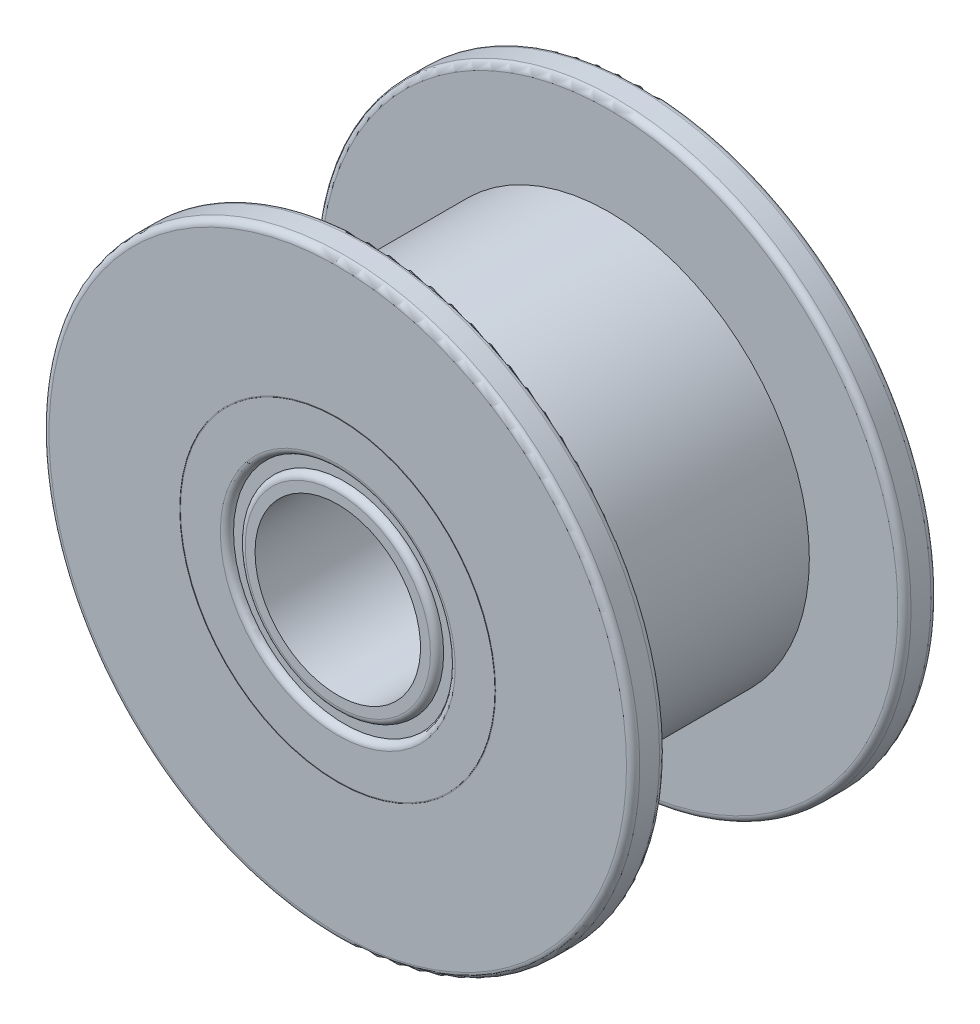
SolidWorks part; units mm, degrees
material "1060-H12 Válcovaný drát (SS)"
ref_plane "Front Plane" through (0, 0, 0) normal (0, 0, 1) x (1, 0, 0)
ref_plane "Top Plane" through (0, 0, 0) normal (0, 1, 0) x (1, 0, 0)
ref_plane "Right Plane" through (0, 0, 0) normal (1, 0, 0) x (0, 0, -1)
sketch "Skica1" plane through (0, 0, 0) normal (0, 0, 1) x (1, 0, 0)
  line L0 (0, 0) -> (0, 6.1) construction
  line L1 (0, 6.1) -> (-0.5, 6.0795) construction
  line L2 (0, 6.1) -> (0.5, 6.0795) construction
  line L3 (-0.5, 6.0795) -> (-0.5, 5.5776)
  line L4 (-0.5, 5.5776) -> (-1.2481, 5.4592) construction
  line L5 (0.5, 6.0795) -> (0.5, 5.5776)
  line L6 (1.4031, 5.9364) -> (1.2481, 5.4592)
  line L7 (2.3542, 5.6274) -> (2.1991, 5.1501)
  line L8 (3.1689, 5.2123) -> (2.8739, 4.8063)
  line L9 (3.9779, 4.6245) -> (3.683, 4.2185)
  line L10 (4.6245, 3.9779) -> (4.2185, 3.683)
  line L11 (5.2123, 3.1689) -> (4.8063, 2.8739)
  line L12 (5.6274, 2.3542) -> (5.1501, 2.1991)
  line L13 (5.9364, 1.4031) -> (5.4592, 1.2481)
  line L14 (6.0795, 0.5) -> (5.5776, 0.5)
  line L15 (6.0795, -0.5) -> (5.5776, -0.5)
  line L16 (5.9364, -1.4031) -> (5.4592, -1.2481)
  line L17 (5.6274, -2.3542) -> (5.1501, -2.1991)
  line L18 (5.2123, -3.1689) -> (4.8063, -2.8739)
  line L19 (4.6245, -3.9779) -> (4.2185, -3.683)
  line L20 (3.9779, -4.6245) -> (3.683, -4.2185)
  line L21 (3.1689, -5.2123) -> (2.8739, -4.8063)
  line L22 (2.3542, -5.6274) -> (2.1991, -5.1501)
  line L23 (1.4031, -5.9364) -> (1.2481, -5.4592)
  line L24 (0.5, -6.0795) -> (0.5, -5.5776)
  line L25 (-0.5, -6.0795) -> (-0.5, -5.5776)
  line L26 (-1.4031, -5.9364) -> (-1.2481, -5.4592)
  line L27 (-2.3542, -5.6274) -> (-2.1991, -5.1501)
  line L28 (-3.1689, -5.2123) -> (-2.8739, -4.8063)
  line L29 (-3.9779, -4.6245) -> (-3.683, -4.2185)
  line L30 (-4.6245, -3.9779) -> (-4.2185, -3.683)
  line L31 (-5.2123, -3.1689) -> (-4.8063, -2.8739)
  line L32 (-5.6274, -2.3542) -> (-5.1501, -2.1991)
  line L33 (-5.9364, -1.4031) -> (-5.4592, -1.2481)
  line L34 (-6.0795, -0.5) -> (-5.5776, -0.5)
  line L35 (-6.0795, 0.5) -> (-5.5776, 0.5)
  line L36 (-5.9364, 1.4031) -> (-5.4592, 1.2481)
  line L37 (-5.6274, 2.3542) -> (-5.1501, 2.1991)
  line L38 (-5.2123, 3.1689) -> (-4.8063, 2.8739)
  line L39 (-4.6245, 3.9779) -> (-4.2185, 3.683)
  line L40 (-3.9779, 4.6245) -> (-3.683, 4.2185)
  line L41 (-3.1689, 5.2123) -> (-2.8739, 4.8063)
  line L42 (-2.3542, 5.6274) -> (-2.1991, 5.1501)
  line L43 (-1.4031, 5.9364) -> (-1.2481, 5.4592)
  circle A0 centre (0, 0) radius 6.1 construction
  circle A1 centre (0, 0) radius 5.6 construction
  arc A2 (-1.2481, 5.4592) -> (-0.5, 5.5776) centre (0, 0) cw
  arc A3 (-0.5, 6.0795) -> (0.5, 6.0795) centre (0, 0) cw
  arc A4 (0.5, 5.5776) -> (1.2481, 5.4592) centre (0, 0) cw
  arc A5 (1.4031, 5.9364) -> (2.3542, 5.6274) centre (0, 0) cw
  arc A6 (2.1991, 5.1501) -> (2.8739, 4.8063) centre (0, 0) cw
  arc A7 (3.1689, 5.2123) -> (3.9779, 4.6245) centre (0, 0) cw
  arc A8 (3.683, 4.2185) -> (4.2185, 3.683) centre (0, 0) cw
  arc A9 (4.6245, 3.9779) -> (5.2123, 3.1689) centre (0, 0) cw
  arc A10 (4.8063, 2.8739) -> (5.1501, 2.1991) centre (0, 0) cw
  arc A11 (5.6274, 2.3542) -> (5.9364, 1.4031) centre (0, 0) cw
  arc A12 (5.4592, 1.2481) -> (5.5776, 0.5) centre (0, 0) cw
  arc A13 (6.0795, 0.5) -> (6.0795, -0.5) centre (0, 0) cw
  arc A14 (5.5776, -0.5) -> (5.4592, -1.2481) centre (0, 0) cw
  arc A15 (5.9364, -1.4031) -> (5.6274, -2.3542) centre (0, 0) cw
  arc A16 (5.1501, -2.1991) -> (4.8063, -2.8739) centre (0, 0) cw
  arc A17 (5.2123, -3.1689) -> (4.6245, -3.9779) centre (0, 0) cw
  arc A18 (4.2185, -3.683) -> (3.683, -4.2185) centre (0, 0) cw
  arc A19 (3.9779, -4.6245) -> (3.1689, -5.2123) centre (0, 0) cw
  arc A20 (2.8739, -4.8063) -> (2.1991, -5.1501) centre (0, 0) cw
  arc A21 (2.3542, -5.6274) -> (1.4031, -5.9364) centre (0, 0) cw
  arc A22 (1.2481, -5.4592) -> (0.5, -5.5776) centre (0, 0) cw
  arc A23 (0.5, -6.0795) -> (-0.5, -6.0795) centre (0, 0) cw
  arc A24 (-0.5, -5.5776) -> (-1.2481, -5.4592) centre (0, 0) cw
  arc A25 (-1.4031, -5.9364) -> (-2.3542, -5.6274) centre (0, 0) cw
  arc A26 (-2.1991, -5.1501) -> (-2.8739, -4.8063) centre (0, 0) cw
  arc A27 (-3.1689, -5.2123) -> (-3.9779, -4.6245) centre (0, 0) cw
  arc A28 (-3.683, -4.2185) -> (-4.2185, -3.683) centre (0, 0) cw
  arc A29 (-4.6245, -3.9779) -> (-5.2123, -3.1689) centre (0, 0) cw
  arc A30 (-4.8063, -2.8739) -> (-5.1501, -2.1991) centre (0, 0) cw
  arc A31 (-5.6274, -2.3542) -> (-5.9364, -1.4031) centre (0, 0) cw
  arc A32 (-5.4592, -1.2481) -> (-5.5776, -0.5) centre (0, 0) cw
  arc A33 (-6.0795, -0.5) -> (-6.0795, 0.5) centre (0, 0) cw
  arc A34 (-5.5776, 0.5) -> (-5.4592, 1.2481) centre (0, 0) cw
  arc A35 (-5.9364, 1.4031) -> (-5.6274, 2.3542) centre (0, 0) cw
  arc A36 (-5.1501, 2.1991) -> (-4.8063, 2.8739) centre (0, 0) cw
  arc A37 (-5.2123, 3.1689) -> (-4.6245, 3.9779) centre (0, 0) cw
  arc A38 (-4.2185, 3.683) -> (-3.683, 4.2185) centre (0, 0) cw
  arc A39 (-3.9779, 4.6245) -> (-3.1689, 5.2123) centre (0, 0) cw
  arc A40 (-2.8739, 4.8063) -> (-2.1991, 5.1501) centre (0, 0) cw
  arc A41 (-2.3542, 5.6274) -> (-1.4031, 5.9364) centre (0, 0) cw
  point P110 (0, 0)
  dimension "D1" = 12.2
  dimension "D2" = 0.5
  dimension "D3" = 1
  dimension "D5" = 20
extrude "Přidat vysunutím1" add sketch "Skica1" along normal blind 7.2
fillet "Zaoblit1" radius 0.2 80 edges at (-2.1991, 5.1501, 3.6) (-2.3542, 5.6274, 3.6) (-1.4031, 5.9364, 3.6) (-1.2481, 5.4592, 3.6) (-0.5, 5.5776, 3.6) (-0.5, 6.0795, 3.6) (0.5, 6.0795, 3.6) (0.5, 5.5776, 3.6) (1.2481, 5.4592, 3.6) (1.4031, 5.9364, 3.6) (2.3542, 5.6274, 3.6) (2.1991, 5.1501, 3.6) (-2.8739, 4.8063, 3.6) (-3.1689, 5.2123, 3.6) (-3.9779, 4.6245, 3.6) (-3.683, 4.2185, 3.6) (-4.2185, 3.683, 3.6) (-4.6245, 3.9779, 3.6) (-5.2123, 3.1689, 3.6) (-4.8063, 2.8739, 3.6) (-5.1501, 2.1991, 3.6) (-5.6274, 2.3542, 3.6) (-5.9364, 1.4031, 3.6) (-5.4592, 1.2481, 3.6) (-5.5776, 0.5, 3.6) (-6.0795, 0.5, 3.6) (-6.0795, -0.5, 3.6) (-5.5776, -0.5, 3.6) (-5.4592, -1.2481, 3.6) (-5.9364, -1.4031, 3.6) (-5.6274, -2.3542, 3.6) (-5.1501, -2.1991, 3.6) (-4.8063, -2.8739, 3.6) (-5.2123, -3.1689, 3.6) (-4.6245, -3.9779, 3.6) (-4.2185, -3.683, 3.6) (-3.683, -4.2185, 3.6) (-3.9779, -4.6245, 3.6) (-3.1689, -5.2123, 3.6) (-2.8739, -4.8063, 3.6) (-2.1991, -5.1501, 3.6) (-2.3542, -5.6274, 3.6) (-1.4031, -5.9364, 3.6) (-1.2481, -5.4592, 3.6) (-0.5, -5.5776, 3.6) (-0.5, -6.0795, 3.6) (0.5, -6.0795, 3.6) (0.5, -5.5776, 3.6) (1.2481, -5.4592, 3.6) (1.4031, -5.9364, 3.6) (2.3542, -5.6274, 3.6) (2.1991, -5.1501, 3.6) (2.8739, -4.8063, 3.6) (3.1689, -5.2123, 3.6) (3.9779, -4.6245, 3.6) (3.683, -4.2185, 3.6) (4.2185, -3.683, 3.6) (4.6245, -3.9779, 3.6) (5.2123, -3.1689, 3.6) (4.8063, -2.8739, 3.6) (5.1501, -2.1991, 3.6) (5.6274, -2.3542, 3.6) (5.9364, -1.4031, 3.6) (5.4592, -1.2481, 3.6) (5.5776, -0.5, 3.6) (6.0795, -0.5, 3.6) (6.0795, 0.5, 3.6) (5.5776, 0.5, 3.6) (5.4592, 1.2481, 3.6) (5.9364, 1.4031, 3.6) (5.6274, 2.3542, 3.6) (5.1501, 2.1991, 3.6) (4.8063, 2.8739, 3.6) (5.2123, 3.1689, 3.6) (4.6245, 3.9779, 3.6) (4.2185, 3.683, 3.6) (3.683, 4.2185, 3.6) (3.9779, 4.6245, 3.6) (2.8739, 4.8063, 3.6) (3.1689, 5.2123, 3.6)
sketch "Skica2" plane through (0, 0, 7.2) normal (0, 0, 1) x (1, 0, 0)
  circle A0 centre (0, 0) radius 8.925
  dimension "D1" = 17.85
extrude "Přidat vysunutím2" add sketch "Skica2" along normal blind 1
sketch "Skica3" plane through (0, 0, 0) normal (0, 0, -1) x (-1, 0, 0)
  circle A0 centre (0, 0) radius 8.925
  dimension "D1" = 17.85
extrude "Přidat vysunutím3" add sketch "Skica3" along normal blind 1
sketch "Skica4" plane through (0, 0, -1) normal (0, 0, -1) x (-1, 0, 0)
  circle A0 centre (0, 0) radius 2.5
  dimension "D1" = 5
sketch "Skica8" plane through (0, 0, 0) normal (0, 1, 0) x (1, 0, 0)
  line L0 (0, 1) -> (0, 0) construction
  line L1 (8.925, 1) -> (-8.925, 1) construction
  circle A0 centre (0, 0.5) radius 2
  point P8 (0, 0.5)
  point P10 (0, 0.5)
  dimension "D1" = 4
sketch "Skica23" plane through (0, 0, -1) normal (0, 0, -1) x (-1, 0, 0)
  circle A0 centre (0, 0) radius 2.5
  dimension "D1" = 5
extrude "Odebrat vysunutím4" cut sketch "Skica23" against normal through all
sketch "Skica25" plane through (0, 0, 8.2) normal (0, 0, 1) x (1, 0, 0)
  circle A0 centre (0, 0) radius 4.75
  circle A1 centre (0, 0) radius 4.775
  dimension "D1" = 9.5
  dimension "D2" = 9.55
extrude "Odebrat vysunutím6" cut sketch "Skica25" against normal blind 0.01
sketch "Skica27" plane through (0, 0, -1) normal (0, 0, -1) x (-1, 0, 0)
  circle A1 centre (0, 0) radius 4.775
  circle A2 centre (0, 0) radius 4.775
  circle A3 centre (0, 0) radius 4.75
  circle A4 centre (0, 0) radius 4.75
  dimension "D1" = 0
  dimension "D2" = 0
extrude "Odebrat vysunutím7" cut sketch "Skica27" against normal blind 0.01
sketch "Skica28" plane through (0, 0, 8.2) normal (0, 0, 1) x (1, 0, 0)
  circle A0 centre (0, 0) radius 3.5
  circle A1 centre (0, 0) radius 2.5
  dimension "D1" = 5
extrude "Přidat vysunutím4" add sketch "Skica28" against normal up to surface (9.2 mm away) up to face at (-4.775, 0, -1)
sketch "Skica29" plane through (0, 0, 8.2) normal (0, 0, 1) x (1, 0, 0)
  circle A0 centre (0, 0) radius 3
  circle A1 centre (0, 0) radius 3.35
  dimension "D1" = 6.7
  dimension "D2" = 6
extrude "Odebrat vysunutím8" cut sketch "Skica29" against normal blind 0.2
sketch "Skica30" plane through (0, 0, -1) normal (0, 0, -1) x (-1, 0, 0)
  circle A1 centre (0, 0) radius 3.35
  circle A2 centre (0, 0) radius 3.35
  circle A3 centre (0, 0) radius 3
  circle A4 centre (0, 0) radius 3
  dimension "D1" = 0
  dimension "D2" = 0
extrude "Odebrat vysunutím9" cut sketch "Skica30" against normal blind 0.2
fillet "Zaoblit2" radius 0.2 4 edges at (-3, 0, -1) (-3.35, 0, -1) (3, 0, 8.2) (3.35, 0, 8.2)
fillet "Zaoblit3" radius 0.2 4 edges at (8.925, 0, 8.2) (8.925, 0, 7.2) (-8.925, 0, 0) (-8.925, 0, -1)
sketch "Szkic1" plane through (0, 0, 0) normal (0, 0, 1) x (1, 0, 0)
  circle A0 centre (0, 0) radius 6.5
  circle A1 centre (0, 0) radius 2.5 construction
  circle A2 centre (0, 0) radius 2.5
extrude "Dodanie-wyciągnięcie1" add sketch "Szkic1" along normal up to next
sketch "Szkic2" plane through (0, 0, 7.2) normal (0, 0, -1) x (-1, 0, 0)
  circle A0 centre (0, 0) radius 6.5 construction
  circle A1 centre (0, 0) radius 6.5
  circle A2 centre (0, 0) radius 6.05
extrude "Wytnij-wyciągnięcie2" cut sketch "Szkic2" along normal up to surface (7.2 mm away) up to face at (-6.5, 0, 0)
